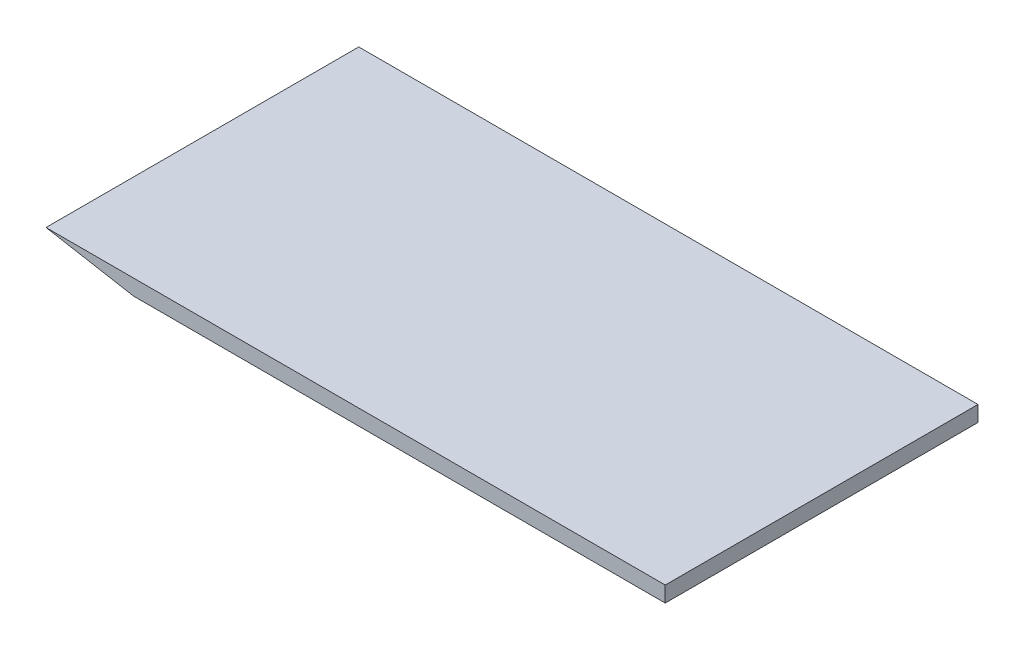
SolidWorks part; units mm, degrees
ref_plane "Front Plane" through (0, 0, 0) normal (0, 0, 1) x (1, 0, 0)
ref_plane "Top Plane" through (0, 0, 0) normal (0, 1, 0) x (1, 0, 0)
ref_plane "Right Plane" through (0, 0, 0) normal (1, 0, 0) x (0, 0, -1)
sketch "Sketch1" plane through (0, 0, 0) normal (0, 0, 1) x (1, 0, 0)
  line L0 (0, 0) -> (198, 0)
  line L1 (198, 0) -> (198, -5)
  line L2 (198, -5) -> (28, -5)
  line L3 (28, -5) -> (0, 0)
  dimension "D1" = 5
  dimension "D2" = 170
  dimension "D3" = 28
extrude "Boss-Extrude1" add sketch "Sketch1" along normal blind 100 contours L3 L0 L1 L2
